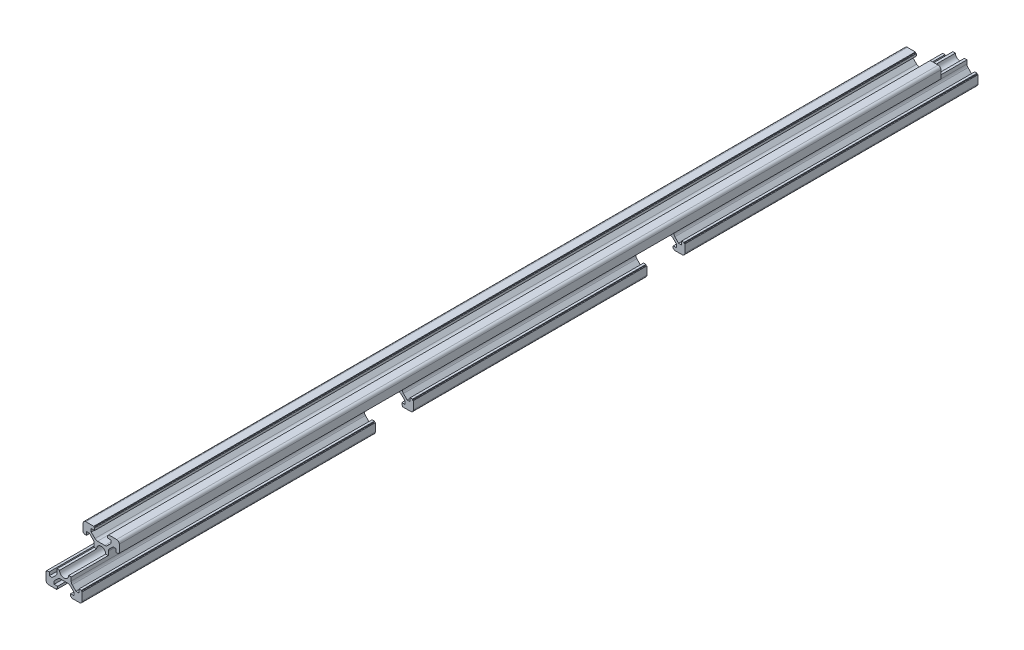
SolidWorks part; units mm, degrees
material "6063-O"
ref_plane "Front Plane" through (0, 0, 0) normal (0, 0, 1) x (1, 0, 0)
ref_plane "Top Plane" through (0, 0, 0) normal (0, 1, 0) x (1, 0, 0)
ref_plane "Right Plane" through (0, 0, 0) normal (1, 0, 0) x (0, 0, -1)
sketch "Sketch1" plane through (0, 0, 0) normal (0, 0, 1) x (1, 0, 0)
  line L0 (10, -4.1) -> (10, -8.5)
  line L1 (4.1, 10) -> (8.5, 10)
  line L2 (8.5, -10) -> (4.1, -10)
  line L3 (-8.5, -10) -> (-4.1, -10)
  line L4 (10, 8.5) -> (10, 4.1)
  line L7 (8.5, 10) -> (4.1, 10)
  line L8 (5.5, 6.5607) -> (3.4251, 4.4858)
  line L9 (8.5, 10) -> (4.1, 10)
  line L10 (3.9, 2.0109) -> (3.9, -2.0109)
  line L11 (2.0109, -3.9) -> (-2.0109, -3.9)
  line L12 (-3.9, -2.0109) -> (-3.9, 2.0109)
  line L13 (-2.0109, 3.9) -> (2.8393, 3.9)
  line L14 (2.5, 0) -> (22.2403, 0) construction
  line L15 (3.6, 9.5) -> (3.6, 8.2)
  line L16 (9.5, 3.6) -> (8.2, 3.6)
  line L17 (8.2, 3.6) -> (8.2, 5.5)
  line L18 (8.2, 5.5) -> (6.5607, 5.5)
  line L19 (10, -4.1) -> (10, -8.5)
  line L20 (4.1, 9.5) -> (3.6, 9.5)
  line L21 (4.1, 10) -> (4.1, 9.5)
  line L22 (8.5, 10) -> (4.1, 10)
  line L23 (10, 4.1) -> (9.5, 4.1)
  line L24 (9.5, 4.1) -> (9.5, 3.6)
  line L25 (5.5, 8.2) -> (5.5, 6.5607)
  line L26 (3.6, 8.2) -> (5.5, 8.2)
  line L27 (4.4858, 3.4251) -> (6.5607, 5.5)
  line L28 (10, -8.5) -> (10, -4.1)
  line L29 (6.5607, -5.5) -> (4.4858, -3.4251)
  line L30 (10, -8.5) -> (10, -4.1)
  line L31 (2.0109, -3.9) -> (-2.0109, -3.9)
  line L32 (3.9, 2.8393) -> (3.9, -2.0109)
  line L33 (9.5, -3.6) -> (8.2, -3.6)
  line L34 (3.6, -9.5) -> (3.6, -8.2)
  line L35 (3.6, -8.2) -> (5.5, -8.2)
  line L36 (5.5, -8.2) -> (5.5, -6.5607)
  line L37 (9.5, -4.1) -> (9.5, -3.6)
  line L38 (10, -4.1) -> (9.5, -4.1)
  line L39 (10, -8.5) -> (10, -4.1)
  line L40 (4.1, -10) -> (4.1, -9.5)
  line L41 (4.1, -9.5) -> (3.6, -9.5)
  line L42 (8.2, -5.5) -> (6.5607, -5.5)
  line L43 (8.2, -3.6) -> (8.2, -5.5)
  line L44 (3.4251, -4.4858) -> (5.5, -6.5607)
  line L45 (-4.1, -10) -> (-8.5, -10)
  line L46 (-10, -8.5) -> (-10, -4.1)
  line L47 (-8.5, -10) -> (-4.1, -10)
  line L48 (-5.5, -6.5607) -> (-3.4251, -4.4858)
  line L49 (-8.5, -10) -> (-4.1, -10)
  line L50 (-3.9, -2.0109) -> (-3.9, 2.0109)
  line L51 (2.0109, -3.9) -> (-2.0109, -3.9)
  line L52 (-3.6, -9.5) -> (-3.6, -8.2)
  line L53 (-9.5, -3.6) -> (-8.2, -3.6)
  line L54 (-8.2, -3.6) -> (-8.2, -5.5)
  line L55 (-8.2, -5.5) -> (-6.5607, -5.5)
  line L56 (-4.1, -9.5) -> (-3.6, -9.5)
  line L57 (-4.1, -10) -> (-4.1, -9.5)
  line L58 (-8.5, -10) -> (-4.1, -10)
  line L59 (-10, -4.1) -> (-9.5, -4.1)
  line L60 (-9.5, -4.1) -> (-9.5, -3.6)
  line L61 (-5.5, -8.2) -> (-5.5, -6.5607)
  line L62 (-3.6, -8.2) -> (-5.5, -8.2)
  line L63 (-4.4858, -3.4251) -> (-6.5607, -5.5)
  line L64 (-10, 4.1) -> (-10, 8.5)
  line L65 (-8.5, 10) -> (-4.1, 10)
  line L66 (-10, 8.5) -> (-10, 4.1)
  line L67 (-6.5607, 5.5) -> (-4.4858, 3.4251)
  line L68 (-10, 8.5) -> (-10, 4.1)
  line L69 (-2.0109, 3.9) -> (2.0109, 3.9)
  line L70 (-3.9, -2.0109) -> (-3.9, 2.0109)
  line L71 (-9.5, 3.6) -> (-8.2, 3.6)
  line L72 (-3.6, 9.5) -> (-3.6, 8.2)
  line L73 (-3.6, 8.2) -> (-5.5, 8.2)
  line L74 (-5.5, 8.2) -> (-5.5, 6.5607)
  line L75 (-9.5, 4.1) -> (-9.5, 3.6)
  line L76 (-10, 4.1) -> (-9.5, 4.1)
  line L77 (-10, 8.5) -> (-10, 4.1)
  line L78 (-4.1, 10) -> (-4.1, 9.5)
  line L79 (-4.1, 9.5) -> (-3.6, 9.5)
  line L80 (-8.2, 5.5) -> (-6.5607, 5.5)
  line L81 (-8.2, 3.6) -> (-8.2, 5.5)
  line L82 (-3.4251, 4.4858) -> (-5.5, 6.5607)
  line L83 (4.1, -10) -> (8.5, -10)
  arc A0 (2.0109, -3.9) -> (3.4251, -4.4858) centre (2.0109, -5.9) cw
  arc A1 (4.4858, -3.4251) -> (3.9, -2.0109) centre (5.9, -2.0109) cw
  arc A2 (3.9, 2.0109) -> (4.4858, 3.4251) centre (5.9, 2.0109) cw
  arc A3 (2.0109, 3.9) -> (3.4251, 4.4858) centre (2.0109, 5.9) ccw
  arc A4 (-2.0109, 3.9) -> (-3.4251, 4.4858) centre (-2.0109, 5.9) cw
  arc A5 (-4.4858, 3.4251) -> (-3.9, 2.0109) centre (-5.9, 2.0109) cw
  arc A6 (-3.4251, -4.4858) -> (-2.0109, -3.9) centre (-2.0109, -5.9) cw
  arc A7 (-3.9, -2.0109) -> (-4.4858, -3.4251) centre (-5.9, -2.0109) cw
  circle A8 centre (0, 0) radius 2.5
  arc A9 (-8.5, -10) -> (-10, -8.5) centre (-8.5, -8.5) cw
  arc A10 (-10, 8.5) -> (-8.5, 10) centre (-8.5, 8.5) cw
  arc A11 (8.5, 10) -> (10, 8.5) centre (8.5, 8.5) cw
  arc A12 (8.5, -10) -> (10, -8.5) centre (8.5, -8.5) ccw
  point P0 (0, 0)
  point P86 (0, 0)
  point P107 (10, -10)
  dimension "D3" = 2
  dimension "D5" = 5
  dimension "D2" = 1.5
  dimension "D8" = 1.5
  dimension "D6" = 4
  dimension "D7" = 6.1
  dimension "D11" = 0.5
  dimension "D12" = 0.5
extrude "Boss-Extrude2" add sketch "Sketch1" along normal blind 495 contours L2 A12 L0 L38 L37 L33 L43 L42 L29 A1 L10 A2 L27 L18 L17 L16 L24 L23 L4 A11 L1 L21 L20 L15 L26 L25 L8 A3 L13 A4 L82 L74 L73 L72 L79 L78 L65 A10 L64 L76 L75 L71 L81 L80 L67 A5 L12 region at (9.7172, -6.3, 0)
sketch "ｽｹｯﾁ1" plane through (-10, 0, 0) normal (-1, 0, 0) x (0, 0, 1)
  line L0 (495, 10) -> (0, 10) construction
  line L10 (247.5, 10) -> (247.5, -66.4608) construction
  line L20 (183, 0) -> (162, 0)
  line L21 (183, 0) -> (183, -10)
  line L22 (183, -10) -> (162, -10)
  line L23 (162, 0) -> (162, -10)
  line L24 (0, 0) -> (20.5, 0)
  line L25 (0, 0) -> (0, 10)
  line L26 (0, 10) -> (20.5, 10)
  line L27 (20.5, 0) -> (20.5, 10)
  line L34 (474.5, 0) -> (495, 0)
  line L52 (474.5, 0) -> (474.5, 10)
  line L53 (474.5, 10) -> (495, 10)
  line L54 (495, 0) -> (495, 10)
  line L55 (495, -10) -> (0, -10) construction
  line L56 (312, -10) -> (333, -10)
  line L57 (312, -10) -> (312, 0)
  line L58 (312, 0) -> (333, 0)
  line L59 (333, -10) -> (333, 0)
  dimension "D1" = 64.5
  dimension "D2" = 21
  dimension "D3" = 64.5
  dimension "D4" = 21
extrude "ｶｯﾄ - 押し出し1" cut sketch "ｽｹｯﾁ1" against normal through all
